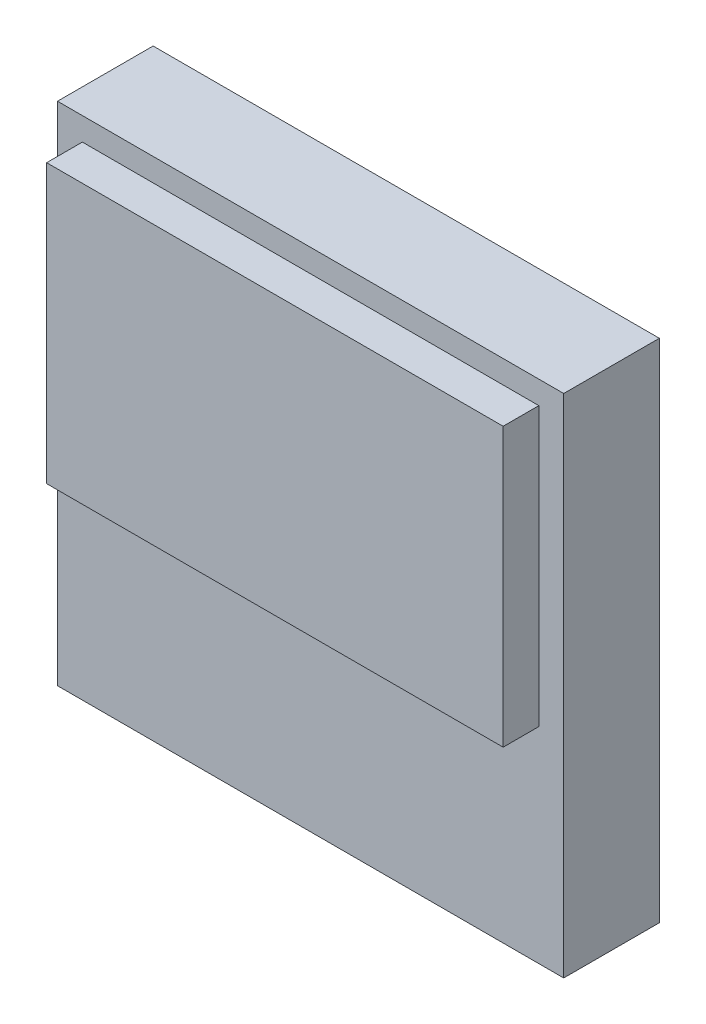
SolidWorks part; units mm, degrees
material "PC High Viscosity"
ref_plane "Front Plane" through (0, 0, 0) normal (0, 0, 1) x (1, 0, 0)
ref_plane "Top Plane" through (0, 0, 0) normal (0, 1, 0) x (1, 0, 0)
ref_plane "Right Plane" through (0, 0, 0) normal (1, 0, 0) x (0, 0, -1)
ref_axis "Axis X" through (57.4134, 0, 0) along (-1, 0, 0)
ref_axis "Axis Y" through (0, 65.1338, 0) along (0, -1, 0)
ref_axis "Axis Z" through (0, 0, -90.83) along (0, 0, 1)
sketch "Sketch1" plane through (0, 0, 0) normal (0, 0, 1) x (1, 0, 0)
  line L1 (19.85, -19.85) -> (19.85, 19.85)
  line L2 (19.85, 19.85) -> (-19.85, 19.85)
  line L3 (-19.85, 19.85) -> (-19.85, -19.85)
  line L4 (-19.85, -19.85) -> (19.85, -19.85)
  circle A0 centre (0, 0) radius 19.85 construction
  dimension "D1" = 39.7
extrude "Boss-Extrude1" add sketch "Sketch1" along normal blind 7.5
sketch "Sketch2" plane through (0, 0, 7.5) normal (0, 0, 1) x (1, 0, 0)
  line L0 (-17.9, 18.05) -> (17.9, -3.75) construction
  line L1 (-17.9, 18.05) -> (17.9, 18.05)
  line L2 (-17.9, 18.05) -> (-17.9, -3.75)
  line L3 (-17.9, -3.75) -> (17.9, -3.75)
  line L4 (17.9, 18.05) -> (17.9, -3.75)
  line L5 (19.85, 19.85) -> (-19.85, 19.85) construction
  point P4 (0, 7.15)
  dimension "D1" = 1.8
  dimension "D2" = 21.8
  dimension "D3" = 35.8
extrude "Boss-Extrude2" add sketch "Sketch2" along normal blind 2.8
shell "Shell1" thickness 0.5 removed face at (0, 0, 0)
sketch "Sketch4" plane through (0, 0, 7) normal (0, 0, -1) x (-1, 0, 0)
  line L0 (-19.35, 19.35) -> (19.35, 19.35) construction
  line L1 (-11.5, 19.35) -> (-10.5, 19.35)
  line L2 (-11.5, 19.35) -> (-11.5, 18.35)
  line L3 (-11.5, 18.35) -> (-10.5, 18.35)
  line L4 (-10.5, 19.35) -> (-10.5, 18.35)
  line L5 (0, 0) -> (0, 24.2364) construction
  line L6 (-11, 18.35) -> (-11, 20.5658) construction
  line L7 (11, 18.35) -> (11, 20.5658) construction
  line L8 (10.5, 19.35) -> (10.5, 18.35)
  line L9 (11.5, 18.35) -> (10.5, 18.35)
  line L10 (11.5, 19.35) -> (11.5, 18.35)
  line L11 (11.5, 19.35) -> (10.5, 19.35)
  dimension "D1" = 22
  dimension "D2" = 1
  dimension "D3" = 1
extrude "Boss-Extrude3" add sketch "Sketch4" along normal blind 5
mirror "Mirror1" about plane through (0, 0, 0) normal (0, 1, 0) of "Boss-Extrude3"
sketch "Sketch5" plane through (0, 0, 7) normal (0, 0, -1) x (-1, 0, 0)
  line L0 (-19.35, -19.35) -> (-19.35, 19.35) construction
  line L1 (-19.35, -6.85) -> (-18.35, -6.85)
  line L2 (-19.35, -6.85) -> (-19.35, -7.85)
  line L3 (-19.35, -7.85) -> (-18.35, -7.85)
  line L4 (-18.35, -6.85) -> (-18.35, -7.85)
  line L5 (0, 0) -> (0, -15.7476) construction
  line L6 (-19.35, -7.35) -> (-16.4423, -7.35) construction
  line L7 (-11.5, -19.35) -> (-19.35, -19.35) construction
  line L8 (19.35, -7.35) -> (16.4423, -7.35) construction
  line L9 (18.35, -6.85) -> (18.35, -7.85)
  line L10 (19.35, -7.85) -> (18.35, -7.85)
  line L11 (19.35, -6.85) -> (19.35, -7.85)
  line L12 (19.35, -6.85) -> (18.35, -6.85)
  dimension "D1" = 12
  dimension "D2" = 1
  dimension "D3" = 1
extrude "Boss-Extrude4" add sketch "Sketch5" along normal blind 5
sketch "Sketch6" plane through (0, 0, 7) normal (0, 0, -1) x (-1, 0, 0)
  line L0 (-19.35, -6.85) -> (-19.35, 19.35) construction
  line L1 (-19.35, -3.7926) -> (19.35, -3.7926)
  line L2 (-19.35, -3.7926) -> (-19.35, -19.35)
  line L3 (-19.35, -19.35) -> (19.35, -19.35)
  line L4 (19.35, -3.7926) -> (19.35, -19.35)
extrude "Boss-Extrude5" add sketch "Sketch6" along normal blind 0.1
